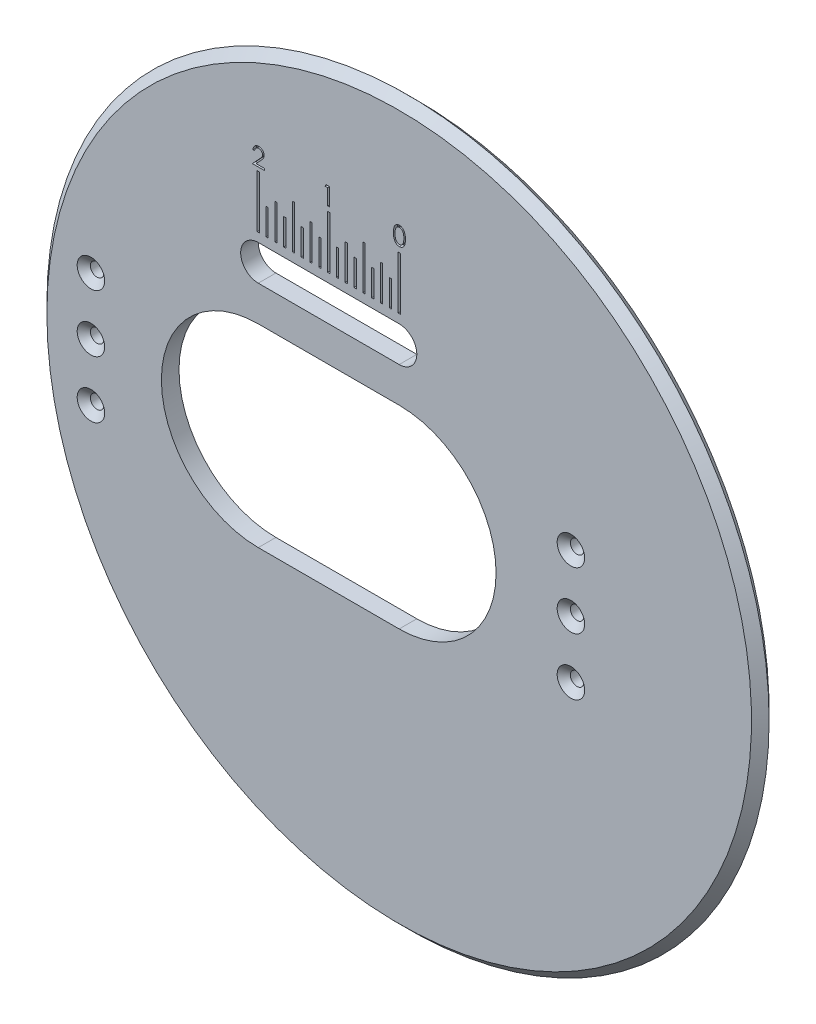
SolidWorks part; units mm, degrees
material "Chrome Stainless Steel"
ref_plane "Front Plane" through (0, 0, 0) normal (0, 0, 1) x (1, 0, 0)
ref_plane "Top Plane" through (0, 0, 0) normal (0, 1, 0) x (1, 0, 0)
ref_plane "Right Plane" through (0, 0, 0) normal (1, 0, 0) x (0, 0, -1)
sketch "Sketch1" plane through (0, 0, 0) normal (0, 0, 1) x (1, 0, 0)
  line L0 (0, 0) -> (-50.8, 0) construction
  line L1 (38.1, -38.1) -> (-38.1, -38.1)
  line L2 (38.1, -38.1) -> (38.1, 38.1)
  line L3 (38.1, 38.1) -> (-38.1, 38.1)
  line L4 (-38.1, -38.1) -> (-38.1, 38.1)
  line L5 (38.1, -38.1) -> (-38.1, 38.1) construction
  line L6 (38.1, 38.1) -> (-38.1, -38.1) construction
  line L7 (0, 0) -> (-63.5, 0) construction
  line L8 (-12.7, 38.1) -> (-88.9, 38.1)
  line L9 (-12.7, 38.1) -> (-12.7, -38.1)
  line L10 (-12.7, -38.1) -> (-88.9, -38.1)
  line L11 (-88.9, 38.1) -> (-88.9, -38.1)
  line L12 (-12.7, 38.1) -> (-88.9, -38.1) construction
  line L13 (-12.7, -38.1) -> (-88.9, 38.1) construction
  line L14 (-50.8, 34.925) -> (12.7, 34.925)
  line L15 (-50.8, -34.925) -> (12.7, -34.925)
  circle A0 centre (0, 0) radius 152.4
  arc A1 (-88.9, 38.1) -> (-88.9, -38.1) centre (-88.9, 0) ccw
  arc A2 (0, 38.1) -> (0, -38.1) centre (0, 0) cw
  circle A3 centre (0, 0) radius 34.925
  circle A4 centre (-50.8, 0) radius 34.925
  dimension "D1" = 304.8
  dimension "D7" = 69.85
  dimension "D9" = 69.85
  dimension "D2" = 76.2
  dimension "D3" = 76.2
  dimension "D4" = 50.8
  dimension "D5" = 76.2
  dimension "D6" = 76.2
  dimension "D8" = 63.5
extrude "Boss-Extrude1" add sketch "Sketch1" along normal blind 6.35 contours A0 L11 L8 L3 L2 L1 L10 | L3 A2 L2 | L2 A2 L1 | L11 A1 | A4 L14 L4 L8 L11 L10 L15 | A3 L15 L9 L1 A2 L3 L14 | L15 L4 L1 L9 | L4 L14 L9 L3 region at (29.5897, -29.5897, 0) region at (-6.35, -37.1842, 0) region at (29.5897, 29.5897, 0) region at (-25.4, -36.5125, 0) region at (-63.5, -37.1842, 0) region at (-25.4, 36.5125, 0) region at (-105.0701, 0, 0) region at (-148.0895, 0, 0)
sketch "Sketch2" plane through (0, 0, 0) normal (0, 0, -1) x (-1, 0, 0)
  line L0 (111.125, 0) -> (50.8, 0) construction
  line L1 (111.125, 0) -> (111.125, -20.6375) construction
  line L2 (111.125, 20.6375) -> (111.125, 0) construction
  circle A1 centre (0, 0) radius 152.4
  circle A2 centre (0, 0) radius 152.4
  circle A5 centre (111.125, 20.6375) radius 2.413
  circle A6 centre (111.125, 0) radius 2.413
  circle A7 centre (111.125, -20.6375) radius 2.413
  dimension "D2" = 60.325
  dimension "D3" = 20.6375
  dimension "D4" = 20.6375
  dimension "D1" = 0
extrude "Cut-Extrude1" cut sketch "Sketch2" against normal blind 10.16 contours A5 | A6 | A7 region at (-111.125, 20.6375, 0) region at (-111.125, 0, 0) region at (-111.125, -20.6375, 0)
sketch "Sketch4" plane through (0, 0, 6.35) normal (0, 0, 1) x (1, 0, 0)
  circle A3 centre (61.8998, 20.6375) radius 2.413
  circle A4 centre (61.8998, 0) radius 2.413
  circle A5 centre (61.8998, -20.6375) radius 2.413
  circle A7 centre (0, 0) radius 152.4
  circle A8 centre (0, 0) radius 152.4
  dimension "D1" = 0
extrude "Cut-Extrude2" cut sketch "Sketch4" against normal blind 7.62 contours A3 | A4 | A5 region at (61.8998, 20.6375, 6.35) region at (61.8998, 0, 6.35)
chamfer "Chamfer1" distance 2.54 angle 41 6 edges at (64.3128, 20.6375, 6.35) (64.3128, 0, 6.35) (64.3128, -20.6375, 6.35) (-108.712, 20.6375, 6.35) (-108.712, 0, 6.35) (-108.712, -20.6375, 6.35) first distance on face at (64.3128, -20.6375, 6.35)
sketch "Sketch6" plane through (0, 0, 0) normal (0, 0, -1) x (-1, 0, 0)
  circle A0 centre (0, 0) radius 127
  circle M11 centre (0, 0) radius 152.4
  dimension "D1" = 254
extrude "Cut-Extrude3" cut sketch "Sketch6" against normal blind 7.62 contours A0 M11 region at (148.0895, 0, 0)
sketch "Sketch5" plane through (0, 0, 0) normal (0, 1, 0) x (1, 0, 0)
  line L0 (-127, -6.35) -> (-127, 0)
  line L1 (-127, 0) -> (-130.175, -3.175)
  line L2 (-130.175, -3.175) -> (-127, -6.35)
  line L3 (0, 0) -> (0, -63.9389) construction
  line L5 (-127, 0) -> (-127, -6.35) construction
  line L6 (-127, -6.35) -> (127, -6.35) construction
  line L7 (127, 0) -> (-127, 0) construction
revolve "Revolve1" add sketch "Sketch5" angle 360 about L3
sketch "Sketch8" plane through (0, 0, 6.35) normal (0, 0, 1) x (1, 0, 0)
  line L0 (-50.8, 34.925) -> (-50.8, 53.975) construction
  line L1 (0, 34.925) -> (0, 53.975) construction
  line L2 (-50.8, 60.325) -> (0, 60.325)
  line L3 (-50.8, 47.625) -> (0, 47.625)
  circle A0 centre (-50.8, 53.975) radius 6.35
  circle A1 centre (0, 53.975) radius 6.35
  dimension "D3" = 12.7
  dimension "D4" = 12.7
  dimension "D1" = 19.05
  dimension "D2" = 19.05
extrude "Cut-Extrude4" cut sketch "Sketch8" against normal blind 7.62 contours A0 | A1 L2 A0 L3 | A1 region at (-25.4, 53.975, 6.35) region at (-50.8, 53.975, 6.35) region at (0, 53.975, 6.35)
sketch "Sketch9" plane through (0, 0, 6.35) normal (0, 0, 1) x (1, 0, 0)
  line L0 (0, 53.975) -> (0, 73.025) construction
  line L1 (-50.8, 70.6438) -> (-44.45, 70.6438) construction
  line L2 (-50.8, 53.975) -> (0, 53.975) construction
  line L3 (-25.4, 53.975) -> (-25.4, 73.025) construction
  line L4 (-50.8, 73.025) -> (-25.4, 73.025) construction
  line L5 (-25.4, 73.025) -> (0, 73.025) construction
  line L6 (-38.1, 73.025) -> (-38.1, 53.975) construction
  line L7 (-12.7, 73.025) -> (-12.7, 53.975) construction
  line L8 (-50.8, 63.5) -> (-38.1, 63.5) construction
  line L9 (-38.1, 63.5) -> (-25.4, 63.5) construction
  line L10 (-25.4, 63.5) -> (-12.7, 63.5) construction
  line L11 (-12.7, 63.5) -> (0, 63.5) construction
  line L12 (-44.45, 63.5) -> (-44.45, 73.025) construction
  line L13 (-31.75, 63.5) -> (-31.75, 73.025) construction
  line L14 (-19.05, 63.5) -> (-19.05, 73.025) construction
  line L15 (-6.35, 63.5) -> (-6.35, 73.025) construction
  line L16 (-44.45, 68.2625) -> (-50.8, 68.2625) construction
  line L17 (-44.45, 68.2625) -> (-38.1, 68.2625) construction
  line L18 (-38.1, 68.2625) -> (-31.75, 68.2625) construction
  line L19 (-31.75, 68.2625) -> (-25.4, 68.2625) construction
  line L20 (-25.4, 68.2625) -> (-19.05, 68.2625) construction
  line L21 (-19.05, 68.2625) -> (-12.7, 68.2625) construction
  line L22 (-12.7, 68.2625) -> (-6.35, 68.2625) construction
  line L23 (-6.35, 68.2625) -> (0, 68.2625) construction
  line L24 (-50.8, 73.025) -> (-50.8, 68.2625) construction
  line L25 (-0.3969, 63.5) -> (0.3969, 63.5)
  line L26 (-0.3969, 63.5) -> (-0.3969, 82.55)
  line L27 (-0.3969, 82.55) -> (0.3969, 82.55)
  line L28 (0.3969, 63.5) -> (0.3969, 82.55)
  line L29 (-0.3969, 63.5) -> (0.3969, 82.55) construction
  line L30 (-0.3969, 82.55) -> (0.3969, 63.5) construction
  line L31 (-51.1969, 63.5) -> (-50.4031, 63.5)
  line L32 (-51.1969, 63.5) -> (-51.1969, 82.55)
  line L33 (-51.1969, 82.55) -> (-50.4031, 82.55)
  line L34 (-50.4031, 63.5) -> (-50.4031, 82.55)
  line L35 (-51.1969, 63.5) -> (-50.4031, 82.55) construction
  line L36 (-51.1969, 82.55) -> (-50.4031, 63.5) construction
  line L37 (-25.7969, 63.5) -> (-25.0031, 63.5)
  line L38 (-25.7969, 63.5) -> (-25.7969, 82.55)
  line L39 (-25.7969, 82.55) -> (-25.0031, 82.55)
  line L40 (-25.0031, 63.5) -> (-25.0031, 82.55)
  line L41 (-25.7969, 63.5) -> (-25.0031, 82.55) construction
  line L42 (-25.7969, 82.55) -> (-25.0031, 63.5) construction
  line L43 (-38.4969, 65.5716) -> (-37.7031, 65.5716)
  line L44 (-38.4969, 65.5716) -> (-38.4969, 79.375)
  line L45 (-38.4969, 79.375) -> (-37.7031, 79.375)
  line L46 (-37.7031, 65.5716) -> (-37.7031, 79.375)
  line L49 (-13.0969, 65.5716) -> (-12.3031, 65.5716)
  line L50 (-13.0969, 65.5716) -> (-13.0969, 79.375)
  line L51 (-13.0969, 79.375) -> (-12.3031, 79.375)
  line L52 (-12.3031, 65.5716) -> (-12.3031, 79.375)
  line L55 (-44.8469, 66.8056) -> (-44.0531, 66.8056)
  line L56 (-44.8469, 66.8056) -> (-44.8469, 76.2)
  line L57 (-44.8469, 76.2) -> (-44.0531, 76.2)
  line L58 (-44.0531, 66.8056) -> (-44.0531, 76.2)
  line L61 (-32.1469, 66.8056) -> (-31.3531, 66.8056)
  line L62 (-32.1469, 66.8056) -> (-32.1469, 76.2)
  line L63 (-32.1469, 76.2) -> (-31.3531, 76.2)
  line L64 (-31.3531, 66.8056) -> (-31.3531, 76.2)
  line L67 (-19.4469, 66.8056) -> (-18.6531, 66.8056)
  line L68 (-19.4469, 66.8056) -> (-19.4469, 76.2)
  line L69 (-19.4469, 76.2) -> (-18.6531, 76.2)
  line L70 (-18.6531, 66.8056) -> (-18.6531, 76.2)
  line L73 (-6.7469, 66.8056) -> (-5.9531, 66.8056)
  line L74 (-6.7469, 66.8056) -> (-6.7469, 76.2)
  line L75 (-6.7469, 76.2) -> (-5.9531, 76.2)
  line L76 (-5.9531, 66.8056) -> (-5.9531, 76.2)
  line L79 (-44.45, 70.6438) -> (-38.1, 70.6438) construction
  line L80 (-38.1, 70.6438) -> (-31.75, 70.6438) construction
  line L81 (-31.75, 70.6438) -> (-25.4, 70.6438) construction
  line L82 (-25.4, 70.6438) -> (-19.05, 70.6438) construction
  line L83 (-19.05, 70.6438) -> (-12.7, 70.6438) construction
  line L84 (-12.7, 70.6438) -> (-6.35, 70.6438) construction
  line L85 (-6.35, 70.6438) -> (0, 70.6438) construction
  line L86 (-3.175, 70.6438) -> (-3.175, 73.025) construction
  line L87 (-9.525, 70.6438) -> (-9.525, 73.025) construction
  line L88 (-15.875, 70.6438) -> (-15.875, 73.025) construction
  line L89 (-22.225, 70.6438) -> (-22.225, 73.025) construction
  line L90 (-28.575, 70.6438) -> (-28.575, 73.025) construction
  line L91 (-34.925, 70.6438) -> (-34.925, 73.025) construction
  line L92 (-41.275, 70.6438) -> (-41.275, 73.025) construction
  line L93 (-47.625, 70.6438) -> (-47.625, 73.025) construction
  line L94 (-50.8, 68.2625) -> (-50.8, 63.5) construction
  line L95 (-50.8, 63.5) -> (-50.8, 53.975) construction
  line L97 (-48.0219, 67.7888) -> (-47.2281, 67.7888)
  line L98 (-48.0219, 67.7888) -> (-48.0219, 73.025)
  line L99 (-48.0219, 73.025) -> (-47.2281, 73.025)
  line L100 (-47.2281, 67.7888) -> (-47.2281, 73.025)
  line L103 (-41.6719, 67.7888) -> (-40.8781, 67.7888)
  line L104 (-41.6719, 67.7888) -> (-41.6719, 73.025)
  line L105 (-41.6719, 73.025) -> (-40.8781, 73.025)
  line L106 (-40.8781, 67.7888) -> (-40.8781, 73.025)
  line L109 (-35.3219, 67.7888) -> (-34.5281, 67.7888)
  line L110 (-35.3219, 67.7888) -> (-35.3219, 73.025)
  line L111 (-35.3219, 73.025) -> (-34.5281, 73.025)
  line L112 (-34.5281, 67.7888) -> (-34.5281, 73.025)
  line L115 (-28.1781, 67.7888) -> (-28.9719, 67.7888)
  line L116 (-28.1781, 67.7888) -> (-28.1781, 73.025)
  line L117 (-28.1781, 73.025) -> (-28.9719, 73.025)
  line L118 (-28.9719, 67.7888) -> (-28.9719, 73.025)
  line L121 (-22.6219, 67.7888) -> (-21.8281, 67.7888)
  line L122 (-22.6219, 67.7888) -> (-22.6219, 73.025)
  line L123 (-22.6219, 73.025) -> (-21.8281, 73.025)
  line L124 (-21.8281, 67.7888) -> (-21.8281, 73.025)
  line L127 (-16.2719, 67.7888) -> (-15.4781, 67.7888)
  line L128 (-16.2719, 67.7888) -> (-16.2719, 73.025)
  line L129 (-16.2719, 73.025) -> (-15.4781, 73.025)
  line L130 (-15.4781, 67.7888) -> (-15.4781, 73.025)
  line L133 (-9.9219, 67.7888) -> (-9.1281, 67.7888)
  line L134 (-9.9219, 67.7888) -> (-9.9219, 73.025)
  line L135 (-9.9219, 73.025) -> (-9.1281, 73.025)
  line L136 (-9.1281, 67.7888) -> (-9.1281, 73.025)
  line L139 (-3.5719, 67.7888) -> (-2.7781, 67.7888)
  line L140 (-3.5719, 67.7888) -> (-3.5719, 73.025)
  line L141 (-3.5719, 73.025) -> (-2.7781, 73.025)
  line L142 (-2.7781, 67.7888) -> (-2.7781, 73.025)
  line L145 (-48.0219, 67.7888) -> (-47.2281, 67.7888)
  line L146 (-48.0219, 67.7888) -> (-48.0219, 63.5)
  line L147 (-48.0219, 63.5) -> (-47.2281, 63.5)
  line L148 (-47.2281, 67.7888) -> (-47.2281, 63.5)
  line L149 (-44.8469, 66.8056) -> (-44.0531, 66.8056)
  line L150 (-44.8469, 66.8056) -> (-44.8469, 63.5)
  line L151 (-44.8469, 63.5) -> (-44.0531, 63.5)
  line L152 (-44.0531, 66.8056) -> (-44.0531, 63.5)
  line L153 (-41.6719, 67.7888) -> (-40.8781, 67.7888)
  line L154 (-41.6719, 67.7888) -> (-41.6719, 63.5)
  line L155 (-41.6719, 63.5) -> (-40.8781, 63.5)
  line L156 (-40.8781, 67.7888) -> (-40.8781, 63.5)
  line L157 (-38.4969, 65.5716) -> (-37.7031, 65.5716)
  line L158 (-38.4969, 65.5716) -> (-38.4969, 63.5)
  line L159 (-38.4969, 63.5) -> (-37.7031, 63.5)
  line L160 (-37.7031, 65.5716) -> (-37.7031, 63.5)
  line L161 (-35.3219, 67.7888) -> (-34.5281, 67.7888)
  line L162 (-35.3219, 67.7888) -> (-35.3219, 63.5)
  line L163 (-35.3219, 63.5) -> (-34.5281, 63.5)
  line L164 (-34.5281, 67.7888) -> (-34.5281, 63.5)
  line L165 (-32.1469, 66.8056) -> (-31.3531, 66.8056)
  line L166 (-32.1469, 66.8056) -> (-32.1469, 63.5)
  line L167 (-32.1469, 63.5) -> (-31.3531, 63.5)
  line L168 (-31.3531, 66.8056) -> (-31.3531, 63.5)
  line L169 (-28.9719, 67.7888) -> (-28.1781, 67.7888)
  line L170 (-28.9719, 67.7888) -> (-28.9719, 63.5)
  line L171 (-28.9719, 63.5) -> (-28.1781, 63.5)
  line L172 (-28.1781, 67.7888) -> (-28.1781, 63.5)
  line L173 (-22.6219, 67.7888) -> (-21.8281, 67.7888)
  line L174 (-22.6219, 67.7888) -> (-22.6219, 63.5)
  line L175 (-22.6219, 63.5) -> (-21.8281, 63.5)
  line L176 (-21.8281, 67.7888) -> (-21.8281, 63.5)
  line L177 (-19.4469, 66.8056) -> (-18.6531, 66.8056)
  line L178 (-19.4469, 66.8056) -> (-19.4469, 63.5)
  line L179 (-19.4469, 63.5) -> (-18.6531, 63.5)
  line L180 (-18.6531, 66.8056) -> (-18.6531, 63.5)
  line L181 (-16.2719, 67.7888) -> (-15.4781, 67.7888)
  line L182 (-16.2719, 67.7888) -> (-16.2719, 63.5)
  line L183 (-16.2719, 63.5) -> (-15.4781, 63.5)
  line L184 (-15.4781, 67.7888) -> (-15.4781, 63.5)
  line L185 (-13.0969, 65.5716) -> (-12.3031, 65.5716)
  line L186 (-13.0969, 65.5716) -> (-13.0969, 63.5)
  line L187 (-13.0969, 63.5) -> (-12.3031, 63.5)
  line L188 (-12.3031, 65.5716) -> (-12.3031, 63.5)
  line L189 (-9.9219, 67.7888) -> (-9.1281, 67.7888)
  line L190 (-9.9219, 67.7888) -> (-9.9219, 63.5)
  line L191 (-9.9219, 63.5) -> (-9.1281, 63.5)
  line L192 (-9.1281, 67.7888) -> (-9.1281, 63.5)
  line L193 (-6.7469, 66.8056) -> (-5.9531, 66.8056)
  line L194 (-6.7469, 66.8056) -> (-6.7469, 63.5)
  line L195 (-6.7469, 63.5) -> (-5.9531, 63.5)
  line L196 (-5.9531, 66.8056) -> (-5.9531, 63.5)
  line L197 (-3.5719, 67.7888) -> (-2.7781, 67.7888)
  line L198 (-3.5719, 67.7888) -> (-3.5719, 63.5)
  line L199 (-3.5719, 63.5) -> (-2.7781, 63.5)
  line L200 (-2.7781, 67.7888) -> (-2.7781, 63.5)
  dimension "D1" = 19.05
  dimension "D2" = 19.05
  dimension "D3" = 19.05
  dimension "D4" = 0.7937
  dimension "D5" = 19.05
  dimension "D6" = 19.05
  dimension "D7" = 19.05
  dimension "D8" = 3.175
  dimension "D9" = 3.175
  dimension "D10" = 3.175
  dimension "D11" = 3.175
  dimension "D12" = 3.175
  dimension "D13" = 3.175
  dimension "D14" = 3.175
  dimension "D15" = 3.175
  dimension "D16" = 3.175
  dimension "D17" = 3.175
  dimension "D18" = 3.175
  dimension "D19" = 3.175
  dimension "D20" = 3.175
  dimension "D21" = 3.175
extrude "Cut-Extrude5" cut sketch "Sketch9" against normal blind 1.27 contours L31 L34 L33 L32 | L148 L97 L146 L147 | L97 L100 L99 L98 | L55 L58 L57 L56 | L152 L55 L150 L151 | L156 L103 L154 L155 | L103 L106 L105 L104 | L43 L46 L45 L44 | L160 L43 L158 L159 | L164 L109 L162 L163 | L109 L112 L111 L110 | L168 L61 L166 L167 | L61 L64 L63 L62 | L118 L115 L116 L117 | L172 L115 L170 L171 | L37 L40 L39 L38 | L176 L121 L174 L175 | L121 L124 L123 L122 | L67 L70 L69 L68 | L180 L67 L178 L179 | L184 L127 L182 L183 | L127 L130 L129 L128 | L188 L49 L186 L187 | L49 L52 L51 L50 | L192 L133 L190 L191 | L133 L136 L135 L134 | L196 L73 L194 L195 | L73 L76 L75 L74 | L200 L139 L198 L199 | L139 L142 L141 L140 | L25 L28 L27 L26 region at (0, 73.025, 6.35) region at (-50.8, 73.025, 6.35) region at (-25.4, 73.025, 6.35) region at (-38.1, 72.4733, 6.35) region at (-38.1, 64.5358, 6.35) region at (-12.7, 72.4733, 6.35) region at (-12.7, 64.5358, 6.35) region at (-44.45, 71.5028, 6.35) region at (-44.45, 65.1528, 6.35) region at (-31.75, 71.5028, 6.35) region at (-31.75, 65.1528, 6.35) region at (-19.05, 71.5028, 6.35) region at (-19.05, 65.1528, 6.35) region at (-6.35, 71.5028, 6.35) region at (-6.35, 65.1528, 6.35) region at (-47.625, 70.4069, 6.35) region at (-47.625, 65.6444, 6.35) region at (-41.275, 70.4069, 6.35) region at (-41.275, 65.6444, 6.35) region at (-34.925, 70.4069, 6.35) region at (-34.925, 65.6444, 6.35) region at (-28.575, 65.6444, 6.35) region at (-28.575, 70.4069, 6.35) region at (-22.225, 70.4069, 6.35) region at (-22.225, 65.6444, 6.35) region at (-15.875, 70.4069, 6.35) region at (-15.875, 65.6444, 6.35) region at (-9.525, 70.4069, 6.35) region at (-9.525, 65.6444, 6.35) region at (-3.175, 70.4069, 6.35) region at (-3.175, 65.6444, 6.35)
sketch "Sketch10" plane through (0, 0, 6.35) normal (0, 0, 1) x (1, 0, 0)
  text T0 "0" font "Century Gothic" height 6.35
extrude "Cut-Extrude6" cut sketch "Sketch10" against normal blind 1.27
sketch "Sketch11" plane through (0, 0, 6.35) normal (0, 0, 1) x (1, 0, 0)
  text T0 "1" font "Century Gothic" height 6.35
extrude "Cut-Extrude7" cut sketch "Sketch11" against normal blind 1.27
sketch "Sketch12" plane through (0, 0, 6.35) normal (0, 0, 1) x (1, 0, 0)
  text T0 "2" font "Century Gothic" height 6.35
extrude "Cut-Extrude8" cut sketch "Sketch12" against normal blind 1.27
ref_axis "carrier plate center axis" through (0, 0, -199.4997) along (0, 0, 1)
sketch "eccentric driveshaft placement" plane through (0, 0, 0) normal (0, 0, 1) x (1, 0, 0)
  line L0 (0, 0) -> (50000, 0) construction
  line L1 (0, 0) -> (32139.3805, -38302.2222) construction
  line L2 (0, 0) -> (38302.2222, 32139.3805) construction
  point P6 (133.2267, -158.7734)
  dimension "D1" = 50
  dimension "D2" = 207.264
  dimension "D3" = 90
ref_plane "shaft plane 1" through (133.2267, -158.7734, 0) normal (0.6428, -0.766, 0) x (-0.766, -0.6428, 0)
ref_plane "shaft plane 2" through (133.2267, -158.7734, 0) normal (0.766, 0.6428, 0) x (0, 0, -1)
